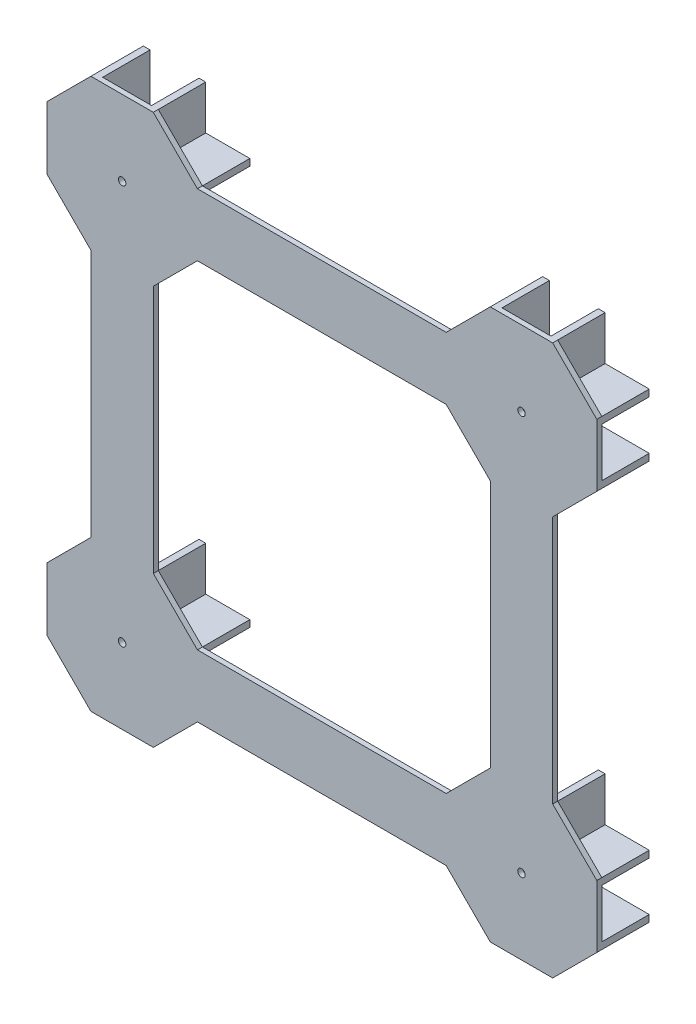
SolidWorks part; units mm, degrees
ref_plane "Front Plane" through (0, 0, 0) normal (0, 0, 1) x (1, 0, 0)
ref_plane "Top Plane" through (0, 0, 0) normal (0, 1, 0) x (1, 0, 0)
ref_plane "Right Plane" through (0, 0, 0) normal (1, 0, 0) x (0, 0, -1)
sketch "Sketch1" plane through (0, 0, 0) normal (0, 0, 1) x (1, 0, 0)
  line L0 (12.5, -110.1777) -> (-12.5, -110.1777)
  line L1 (-12.5, -110.1777) -> (-30.1777, -92.5)
  line L3 (-30.1777, -67.5) -> (-12.5, -49.8223)
  line L5 (12.5, -49.8223) -> (30.1777, -67.5)
  line L6 (30.1777, -67.5) -> (30.1777, -92.5)
  line L7 (30.1777, -92.5) -> (12.5, -110.1777)
  line L8 (9.5, 250) -> (9.5, -250) construction
  line L9 (-9.5, 250) -> (-9.5, -250) construction
  line L10 (9.5, -89.5) -> (170, -89.5) construction
  line L11 (-147.5, -110.1777) -> (-172.5, -110.1777)
  line L12 (-172.5, -110.1777) -> (-190.1777, -92.5)
  line L13 (-190.1777, -92.5) -> (-190.1777, -67.5)
  line L14 (-190.1777, -67.5) -> (-172.5, -49.8223)
  line L16 (-147.5, -49.8223) -> (-129.8223, -67.5)
  line L18 (-129.8223, -92.5) -> (-147.5, -110.1777)
  line L20 (-172.5, 49.8223) -> (-190.1777, 67.5)
  line L21 (-190.1777, 67.5) -> (-190.1777, 92.5)
  line L22 (-190.1777, 92.5) -> (-172.5, 110.1777)
  line L23 (-172.5, 110.1777) -> (-147.5, 110.1777)
  line L24 (-147.5, 110.1777) -> (-129.8223, 92.5)
  line L25 (-129.8223, 92.5) -> (-129.8223, 67.5) construction
  line L26 (-129.8223, 67.5) -> (-147.5, 49.8223)
  line L27 (12.5, 49.8223) -> (-12.5, 49.8223)
  line L28 (-12.5, 49.8223) -> (-30.1777, 67.5)
  line L30 (-30.1777, 92.5) -> (-12.5, 110.1777)
  line L31 (-12.5, 110.1777) -> (12.5, 110.1777)
  line L32 (12.5, 110.1777) -> (30.1777, 92.5)
  line L33 (30.1777, 92.5) -> (30.1777, 67.5)
  line L34 (30.1777, 67.5) -> (12.5, 49.8223)
  line L37 (-172.5, 49.8223) -> (-172.5, -49.8223)
  line L39 (-147.5, 49.8223) -> (-147.5, -49.8223)
  line L40 (-12.5, 49.8223) -> (12.5, 49.8223)
  line L41 (-12.5, 49.8223) -> (-12.5, -49.8223)
  line L43 (12.5, 49.8223) -> (12.5, -49.8223)
  line L44 (-30.1777, -67.5) -> (-129.8223, -67.5)
  line L46 (-30.1777, -92.5) -> (-129.8223, -92.5)
  line L48 (-129.8223, 67.5) -> (-30.1777, 67.5)
  line L49 (-129.8223, 67.5) -> (-129.8223, 92.5) construction
  line L50 (-129.8223, 92.5) -> (-30.1777, 92.5)
  line L54 (-129.8223, -67.5) -> (-129.8223, -92.5) [skipped]
  line L55 (-147.5, 49.8223) -> (-172.5, 49.8223) [skipped]
  dimension "D1" = 3
  dimension "D2" = 3
  dimension "D3" = 135
  dimension "D4" = 3
  dimension "D5" = 2
  dimension "D6" = 2
extrude "Boss-Extrude1" add sketch "Sketch1" along normal blind 2 contours L50 L24 L23 L22 L21 L20 L37 L14 L13 L12 L11 L18 L46 L1 L0 L7 L6 L5 L43 L41 L3 L44 L16 L39 L26 L48 L28 L34 L33 L32 L31 L30 region at (0, -107.9149, 0) region at (-160, -43.824, 0) region at (-80, 80, 0)
sketch "Sketch2" plane through (0, 0, 0) normal (0, 0, -1) x (-1, 0, 0)
  line L0 (30.1777, -67.5) -> (12.5, -67.5)
  line L1 (12.5, -67.5) -> (12.5, -49.8223)
  line L2 (12.5, -49.8223) -> (9.8, -49.8223)
  line L4 (9.8, -49.8223) -> (9.8, -70.2)
  line L5 (9.8, -70.2) -> (30.1777, -70.2)
  line L7 (30.1777, -70.2) -> (30.1777, -67.5)
  line L8 (9.5, 250) -> (9.5, -250) construction
  line L9 (12.5, -92.5) -> (30.1777, -92.5)
  line L10 (30.1777, -92.5) -> (30.1777, -89.8)
  line L11 (30.1777, -89.8) -> (9.8, -89.8)
  line L12 (12.5, -110.1777) -> (12.5, -92.5)
  line L13 (9.8, -110.1777) -> (12.5, -110.1777)
  line L14 (9.8, -89.8) -> (9.8, -110.1777)
  line L15 (-12.5, -92.5) -> (-12.5, -110.1777)
  line L16 (-12.5, -110.1777) -> (-9.8, -110.1777)
  line L17 (-9.8, -110.1777) -> (-9.8, -89.8)
  line L18 (-30.1777, -92.5) -> (-12.5, -92.5)
  line L19 (-30.1777, -89.8) -> (-30.1777, -92.5)
  line L20 (-9.8, -89.8) -> (-30.1777, -89.8)
  line L21 (-12.5, -67.5) -> (-30.1777, -67.5)
  line L22 (-30.1777, -67.5) -> (-30.1777, -70.2)
  line L23 (-30.1777, -70.2) -> (-9.8, -70.2)
  line L24 (-12.5, -49.8223) -> (-12.5, -67.5)
  line L25 (-9.8, -49.8223) -> (-12.5, -49.8223)
  line L26 (-9.8, -70.2) -> (-9.8, -49.8223)
  line L27 (190.1777, -67.5) -> (172.5, -67.5)
  line L28 (172.5, -67.5) -> (172.5, -49.8223)
  line L29 (172.5, -49.8223) -> (169.8, -49.8223)
  line L30 (169.8, -49.8223) -> (169.8, -70.2)
  line L31 (169.8, -70.2) -> (190.1777, -70.2)
  line L32 (190.1777, -70.2) -> (190.1777, -67.5)
  line L33 (172.5, -92.5) -> (190.1777, -92.5)
  line L34 (190.1777, -92.5) -> (190.1777, -89.8)
  line L35 (190.1777, -89.8) -> (169.8, -89.8)
  line L36 (172.5, -110.1777) -> (172.5, -92.5)
  line L37 (169.8, -110.1777) -> (172.5, -110.1777)
  line L38 (169.8, -89.8) -> (169.8, -110.1777)
  line L39 (147.5, -92.5) -> (147.5, -110.1777)
  line L40 (147.5, -110.1777) -> (150.2, -110.1777)
  line L41 (150.2, -110.1777) -> (150.2, -89.8)
  line L42 (129.8223, -92.5) -> (147.5, -92.5)
  line L43 (129.8223, -89.8) -> (129.8223, -92.5)
  line L44 (150.2, -89.8) -> (129.8223, -89.8)
  line L45 (147.5, -67.5) -> (129.8223, -67.5)
  line L46 (129.8223, -67.5) -> (129.8223, -70.2)
  line L47 (129.8223, -70.2) -> (150.2, -70.2)
  line L48 (147.5, -49.8223) -> (147.5, -67.5)
  line L49 (150.2, -49.8223) -> (147.5, -49.8223)
  line L50 (150.2, -70.2) -> (150.2, -49.8223)
  line L51 (190.1777, 92.5) -> (172.5, 92.5)
  line L52 (172.5, 92.5) -> (172.5, 110.1777)
  line L53 (172.5, 110.1777) -> (169.8, 110.1777)
  line L54 (169.8, 110.1777) -> (169.8, 89.8)
  line L55 (169.8, 89.8) -> (190.1777, 89.8)
  line L56 (190.1777, 89.8) -> (190.1777, 92.5)
  line L57 (172.5, 67.5) -> (190.1777, 67.5)
  line L58 (190.1777, 67.5) -> (190.1777, 70.2)
  line L59 (190.1777, 70.2) -> (169.8, 70.2)
  line L60 (172.5, 49.8223) -> (172.5, 67.5)
  line L61 (169.8, 49.8223) -> (172.5, 49.8223)
  line L62 (169.8, 70.2) -> (169.8, 49.8223)
  line L63 (147.5, 67.5) -> (147.5, 49.8223)
  line L64 (147.5, 49.8223) -> (150.2, 49.8223)
  line L65 (150.2, 49.8223) -> (150.2, 70.2)
  line L66 (129.8223, 67.5) -> (147.5, 67.5)
  line L67 (129.8223, 70.2) -> (129.8223, 67.5)
  line L68 (150.2, 70.2) -> (129.8223, 70.2)
  line L69 (147.5, 92.5) -> (129.8223, 92.5)
  line L70 (129.8223, 92.5) -> (129.8223, 89.8)
  line L71 (129.8223, 89.8) -> (150.2, 89.8)
  line L72 (147.5, 110.1777) -> (147.5, 92.5)
  line L73 (150.2, 110.1777) -> (147.5, 110.1777)
  line L74 (150.2, 89.8) -> (150.2, 110.1777)
  line L75 (30.1777, 92.5) -> (12.5, 92.5)
  line L76 (12.5, 92.5) -> (12.5, 110.1777)
  line L77 (12.5, 110.1777) -> (9.8, 110.1777)
  line L78 (9.8, 110.1777) -> (9.8, 89.8)
  line L79 (9.8, 89.8) -> (30.1777, 89.8)
  line L80 (30.1777, 89.8) -> (30.1777, 92.5)
  line L81 (12.5, 67.5) -> (30.1777, 67.5)
  line L82 (30.1777, 67.5) -> (30.1777, 70.2)
  line L83 (30.1777, 70.2) -> (9.8, 70.2)
  line L84 (12.5, 49.8223) -> (12.5, 67.5)
  line L85 (9.8, 49.8223) -> (12.5, 49.8223)
  line L86 (9.8, 70.2) -> (9.8, 49.8223)
  line L87 (-12.5, 67.5) -> (-12.5, 49.8223)
  line L88 (-12.5, 49.8223) -> (-9.8, 49.8223)
  line L89 (-9.8, 49.8223) -> (-9.8, 70.2)
  line L90 (-30.1777, 67.5) -> (-12.5, 67.5)
  line L91 (-30.1777, 70.2) -> (-30.1777, 67.5)
  line L92 (-9.8, 70.2) -> (-30.1777, 70.2)
  line L93 (-12.5, 92.5) -> (-30.1777, 92.5)
  line L94 (-30.1777, 92.5) -> (-30.1777, 89.8)
  line L95 (-30.1777, 89.8) -> (-9.8, 89.8)
  line L96 (-12.5, 110.1777) -> (-12.5, 92.5)
  line L97 (-9.8, 110.1777) -> (-12.5, 110.1777)
  line L98 (-9.8, 89.8) -> (-9.8, 110.1777)
  circle A0 centre (0, -80) radius 30.1777 construction
  circle A1 centre (160, -80) radius 30.1777 construction
  circle A2 centre (160, 80) radius 30.1777 construction
  circle A3 centre (0, 80) radius 30.1777 construction
  point P38 (0, -80)
  point P61 (160, -80)
  point P88 (160, 80)
  point P115 (0, 80)
  dimension "D1" = 0.3
  dimension "D3" = 2
  dimension "D4" = 2
  dimension "D2" = 4
extrude "Boss-Extrude2" add sketch "Sketch2" along normal blind 19
sketch "Sketch6" plane through (0, 0, 2) normal (0, 0, 1) x (1, 0, 0)
  line L0 (-172.5, 49.8223) -> (-190.1777, 67.5) construction
  line L1 (-129.8223, 67.5) -> (-147.5, 49.8223) construction
  line L2 (-172.5, 110.1777) -> (-147.5, 110.1777) construction
  line L3 (-147.5, -49.8223) -> (-129.8223, -67.5) construction
  line L4 (-147.5, -110.1777) -> (-172.5, -110.1777) construction
  line L5 (-190.1777, -67.5) -> (-172.5, -49.8223) construction
  line L6 (12.5, -110.1777) -> (-12.5, -110.1777) construction
  line L7 (30.1777, -67.5) -> (30.1777, -92.5) construction
  line L8 (-30.1777, -67.5) -> (-12.5, -49.8223) construction
  line L9 (-30.1777, 92.5) -> (-12.5, 110.1777) construction
  line L10 (-12.5, 49.8223) -> (-30.1777, 67.5) construction
  line L11 (30.1777, 92.5) -> (30.1777, 67.5) construction
  circle A0 centre (-160, -80) radius 30.1777 construction
  circle A1 centre (-160, 80) radius 30.1777 construction
  circle A2 centre (0, 80) radius 30.1777 construction
  circle A3 centre (0, -80) radius 30.1777 construction
  circle A4 centre (-160, 80) radius 1.5
  circle A5 centre (0, 80) radius 1.5
  circle A6 centre (-160, -80) radius 1.5
  circle A7 centre (0, -80) radius 1.5
  dimension "D1" = 3
extrude "Cut-Extrude1" cut sketch "Sketch6" against normal through all
